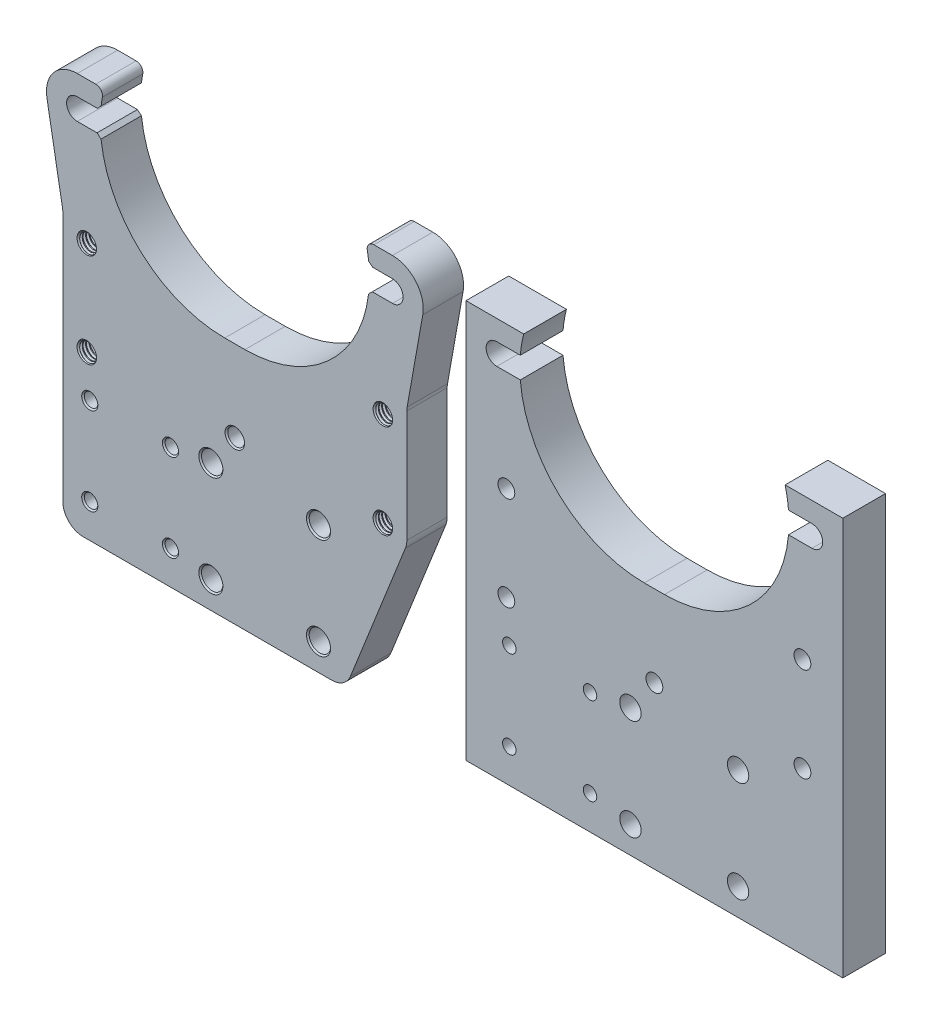
SolidWorks part; units mm, degrees
ref_plane "Front Plane" through (0, 0, 0) normal (0, 0, 1) x (1, 0, 0)
ref_plane "Top Plane" through (0, 0, 0) normal (0, 1, 0) x (1, 0, 0)
ref_plane "Right Plane" through (0, 0, 0) normal (1, 0, 0) x (0, 0, -1)
sketch "Sketch1" plane through (0, 0, 0) normal (0, 0, 1) x (1, 0, 0)
  line L0 (-8, 7.5) -> (8, 7.5) construction
  line L5 (-26, 6.5) -> (-14, 6.5) construction
  line L7 (-8, -7.5) -> (8, -7.5) construction
  line L8 (-8, -7.5) -> (-8, 7.5) construction
  line L9 (-8, 7.5) -> (8, 7.5) construction
  line L10 (8, -7.5) -> (8, 7.5) construction
  line L11 (-8, -7.5) -> (8, 7.5) construction
  line L12 (-8, 7.5) -> (8, -7.5) construction
  line L13 (-8, 7.5) -> (-8, -7.5) construction
  line L14 (-26, -6.5) -> (-14, -6.5) construction
  line L15 (-26, -6.5) -> (-26, 6.5) construction
  line L16 (-26, 6.5) -> (-14, 6.5) construction
  line L17 (-14, -6.5) -> (-14, 6.5) construction
  line L18 (-26, -6.5) -> (-14, 6.5) construction
  line L19 (-26, 6.5) -> (-14, -6.5) construction
  line L20 (0, 0) -> (-20, 0) construction
  line L21 (-6.4375, 59.6343) -> (-6.4375, -58.2445) construction
  line L22 (-30, -11.5) -> (12, -11.5)
  line L23 (-30, -11.5) -> (-30, 11.5)
  line L24 (-30, 11.5) -> (12, 11.5)
  line L25 (12, -11.5) -> (12, 11.5)
  line L26 (-30, -11.5) -> (12, 11.5) construction
  line L27 (-30, 11.5) -> (12, -11.5) construction
  line L28 (-11.5, -15) -> (-28.5, -15) construction
  line L29 (-11.5, -15) -> (-11.5, 15) construction
  line L30 (-11.5, 15) -> (-28.5, 15) construction
  line L31 (-28.5, -15) -> (-28.5, 15) construction
  line L32 (-11.5, -15) -> (-28.5, 15) construction
  line L33 (-11.5, 15) -> (-28.5, -15) construction
  line L34 (-59, 15) -> (41, 15) construction
  line L35 (-59, 15) -> (-59, 24) construction
  line L36 (-59, 24) -> (41, 24) construction
  line L37 (41, 15) -> (41, 24) construction
  line L38 (-59, -10) -> (41, -10) construction
  line L39 (-59, -10) -> (-59, 10) construction
  line L40 (-59, 10) -> (41, 10) construction
  line L41 (41, -10) -> (41, 10) construction
  line L42 (-59, -10) -> (41, 10) construction
  line L43 (-59, 10) -> (41, -10) construction
  line L44 (-30, -11.5) -> (12, -11.5)
  line L45 (-30, -11.5) -> (-30, 29)
  line L46 (-30, 29) -> (12, 29)
  line L47 (12, -11.5) -> (12, 29)
  line L48 (-4.4375, 43.1) -> (17.4825, 43.1) construction
  line L49 (-4.4375, 43.1) -> (-26.3575, 43.1) construction
  line L50 (-24.8575, 43.1) -> (-27.8575, 43.1) construction
  line L51 (-24.8575, 41.5125) -> (-27.8575, 41.5125)
  line L52 (-24.8575, 44.6875) -> (-27.8575, 44.6875)
  line L53 (15.9825, 43.1) -> (18.9825, 43.1) construction
  line L54 (15.9825, 44.6875) -> (18.9825, 44.6875)
  line L55 (15.9825, 41.5125) -> (18.9825, 41.5125)
  line L56 (-24.8575, 44.6875) -> (-22.8693, 44.6875)
  line L57 (-24.8575, 41.5125) -> (-22.8693, 41.5125)
  line L58 (15.9825, 41.5125) -> (13.9943, 41.5125)
  line L59 (15.9825, 44.6875) -> (13.9943, 44.6875)
  line L60 (-4.4375, 43.1) -> (-4.4375, 61.6) construction
  line L61 (12, -11.5) -> (21.125, 11.5)
  line L62 (21.125, 11.5) -> (21.125, 29)
  line L63 (21.125, 29) -> (12, 29)
  line L64 (18.9825, 47.68) -> (14.874, 47.68)
  line L65 (21.125, 29) -> (23.4916, 42.2975)
  line L66 (-30, 29) -> (-32.3666, 42.2975)
  line L67 (-5.9375, 43.1) -> (-2.9375, 43.1) construction
  line L68 (-5.9375, 61.6) -> (-2.9375, 61.6)
  line L69 (-5.9375, 24.6) -> (-2.9375, 24.6)
  line L70 (23.5625, -11.5) -> (13.5725, -7.5366) construction
  line L71 (-32.4375, 47.68) -> (23.5625, 47.68)
  line L72 (-6.4375, 19.5) -> (6.6756, 19.5) construction
  line L73 (-27.8575, 47.68) -> (-23.8616, 47.68)
  line L74 (-32.4375, 47.68) -> (-32.4375, -11.5)
  line L75 (-32.4375, -11.5) -> (23.5625, -11.5)
  line L76 (23.5625, 47.68) -> (23.5625, -11.5)
  circle A0 centre (-8, 7.5) radius 1.5875
  circle A2 centre (8, 7.5) radius 1.5875
  circle A3 centre (8, -7.5) radius 1.5875
  circle A4 centre (-8, -7.5) radius 1.5875
  circle A5 centre (-26, 6.5) radius 1
  circle A6 centre (-14, 6.5) radius 1
  circle A7 centre (-14, -6.5) radius 1
  circle A8 centre (-26, -6.5) radius 1
  circle A9 centre (-8, 7.5) radius 2.9 construction
  circle A10 centre (-14, 6.5) radius 2
  circle A11 centre (-26, 6.5) radius 2
  circle A12 centre (-26, -6.5) radius 2
  circle A13 centre (-14, -6.5) radius 2
  circle A14 centre (-4.4375, 43.1) radius 2 construction
  circle A15 centre (-4.4375, 43.1) radius 8 construction
  circle A16 centre (-4.4375, 43.1) radius 18.5
  circle A17 centre (17.4825, 43.1) radius 1.5875 construction
  circle A18 centre (-26.3575, 43.1) radius 1.5875 construction
  arc A19 (-24.8575, 41.5125) -> (-24.8575, 44.6875) centre (-24.8575, 43.1) ccw
  arc A20 (-27.8575, 44.6875) -> (-27.8575, 41.5125) centre (-27.8575, 43.1) ccw
  arc A21 (15.9825, 44.6875) -> (15.9825, 41.5125) centre (15.9825, 43.1) ccw
  arc A22 (18.9825, 41.5125) -> (18.9825, 44.6875) centre (18.9825, 43.1) ccw
  arc A23 (-5.9375, 61.6) -> (-5.9375, 24.6) centre (-5.9375, 43.1) ccw
  arc A24 (-2.9375, 24.6) -> (-2.9375, 61.6) centre (-2.9375, 43.1) ccw
  circle A25 centre (-26.4375, 26.5) radius 1.25
  circle A26 centre (-26.4375, 12.5) radius 1.25
  circle A29 centre (17.5625, 12.5) radius 1.25
  circle A30 centre (17.5625, 26.5) radius 1.25
  circle A31 centre (-27.8575, 43.1) radius 4.58
  circle A32 centre (18.9825, 43.1) radius 4.58
  circle A33 centre (17.5625, 26.5) radius 2.9 construction
  circle A34 centre (17.5625, 12.5) radius 2.9 construction
  circle A35 centre (-4.4375, 12.5) radius 1.25
  point P0 (0, 0)
  point P1 (-20, 0)
  point P4 (-9, 0)
  point P6 (0, 0)
  point P46 (-9, 15)
  point P47 (-9, 0)
  point P70 (-26.3575, 43.1)
  point P77 (17.4825, 43.1)
  point P97 (-4.4375, 43.1)
  dimension "D5" = 3.175
  dimension "D6" = 2
  dimension "D18" = 5.8
  dimension "D27" = 4
  dimension "D29" = 4
  dimension "D30" = 16
  dimension "D31" = 37
  dimension "D33" = 3.175
  dimension "D35" = 1.5875
  dimension "D40" = 18.5
  dimension "D43" = 2.5
  dimension "D39" = 9.16
  dimension "D48" = 9.16
  dimension "D38" = 5.8
  dimension "D42" = 2.5
  dimension "D1" = 15
  dimension "D2" = 16
  dimension "D3" = 13
  dimension "D4" = 12
  dimension "D9" = 16
  dimension "D10" = 15
  dimension "D13" = 12
  dimension "D14" = 20
  dimension "D15" = 23
  dimension "D16" = 4
  dimension "D17" = 4
  dimension "D19" = 17
  dimension "D20" = 30
  dimension "D21" = 9
  dimension "D22" = 100
  dimension "D23" = 20
  dimension "D24" = 100
  dimension "D25" = 15
  dimension "D26" = 40.5
  dimension "D28" = 13.5625
  dimension "D32" = 21.92
  dimension "D34" = 19.1
  dimension "D36" = 3
  dimension "D37" = 9.125
  dimension "D41" = 3
  dimension "D44" = 20
  dimension "D45" = 4.5
  dimension "D46" = 7
  dimension "D47" = 7
  dimension "D49" = 22
  dimension "D7" = 2
  dimension "D8" = 2
  dimension "D11" = 2
  dimension "D12" = 2
extrude "Boss-Extrude1" add sketch "Sketch1" along normal blind 6 contours A20 L52 L56 A16 L46 L57 L51 | A22 L55 L58 A16 L46 L63 L59 L54 | L62 L63 L47 L25 L61 | A16 L46 L45 L24 L47 | L22 L25 L24 L23 A13 A12 A11 A10 A4 A3 A2 A0 | A10 A6 | A11 A5 | A12 A8 | A13 A7 | A31 L46 A23 | A32 A24 L46 L63 | A31 A23 L73 | A32 L64 A24 region at (-8.6931, -0.0066, 0) region at (15.8976, 13.518, 0) region at (-9.3836, 19.3871, 0) region at (-26.1981, 33.733, 0) region at (-31.0091, 46.2516, 0) region at (17.3231, 33.733, 0) region at (23.4222, 42.708, 0) region at (-24.9644, 47.1601, 0) region at (16.0894, 47.1601, 0) region at (-15.9434, 6.5, 0) region at (-27.9434, 6.5, 0) region at (-27.9434, -6.5, 0) region at (-15.9434, -6.5, 0)
extrude "Cut-Extrude1" cut sketch "Sketch1<3>" along normal blind 2.2 contours A10 A6 | A11 A5 | A12 A8 | A13 A7 | A13 region at (-15.9434, 6.5, 0) region at (-27.9434, 6.5, 0) region at (-27.9434, -6.5, 0) region at (-15.9434, -6.5, 0)
sketch "Sketch1<3>" plane through (0, 0, 0) normal (0, 0, 1) x (1, 0, 0) same geometry as "Sketch1"
chamfer "Chamfer1" distance 0.2 angle 45 26 edges at (-24, 6.5, 0) (-24, -6.5, 0) (-12, -6.5, 0) (-12, 6.5, 0) (-6.4125, -7.5, 0) (9.5875, -7.5, 0) (9.5875, 7.5, 0) (-6.4125, 7.5, 0) (-25, -6.5, 6) (-25, 6.5, 6) (-13, 6.5, 6) (-13, -6.5, 6) (-6.4125, -7.5, 6) (9.5875, -7.5, 6) (9.5875, 7.5, 6) (-6.4125, 7.5, 6) (18.8125, 26.5, 0) (18.8125, 26.5, 6) (18.8125, 12.5, 0) (18.8125, 12.5, 6) (-25.1875, 12.5, 0) (-25.1875, 12.5, 6) (-25.1875, 26.5, 0) (-25.1875, 26.5, 6) (-3.1875, 12.5, 0) (-3.1875, 12.5, 6)
fillet "Fillet1" radius 3 5 edges at (-30, -11.5, 3) (12, -11.5, 3) (21.125, 11.5, 3) (21.125, 29, 3) (-30, 29, 3)
chamfer "Chamfer2" distance 0.5 angle 45 4 edges at (-24.3693, 41.5125, 3) (-24.3693, 44.6875, 3) (15.4943, 44.6875, 3) (15.4943, 41.5125, 3) first distance on face at (-16.7993, 31.2625, 3) first distance on face at (-26.1134, 44.6875, 3) first distance on face at (15.2712, 46.189, 3) first distance on face at (17.2384, 41.5125, 3)
fillet "Fillet4" radius 1 2 edges at (-23.8616, 47.68, 3) (14.9866, 47.68, 3)
thread "Thread1" pitch 0.5 method cut profile "Thread Profile1" start angle 0, offset 1, length 10, pitch 0.5, diameter 2.5
ref_plane "Plane1" through (-27.6875, 26.5, 6.8) normal (0, -1, 0) x (-1, 0, 0)
sketch "Thread Profile1" plane through (-27.6875, 26.5, 6.8) normal (0, -1, 0) x (-1, 0, 0)
  line L0 (0, 0) -> (0, 0.5) construction
  line L1 (0, 0) -> (0.2706, 0.1562)
  line L2 (0.2706, 0.1562) -> (0.2706, 0.2187)
  line L3 (0.2706, 0.2187) -> (0, 0.375)
  line L4 (0.2706, 0.1875) -> (0, 0.1875) construction
  line L11 (0, 0) -> (0, 0.375)
  point P2 (0, 0)
  dimension "Pitch" = 0.5
  dimension "Profile_Angle" = 60
  dimension "Profile_Land" = 0.0625
  dimension "Profile_Height" = 0.2706
pattern_linear "LPattern1" count 2 spacing 44 along (1, 0, 0) count 2 spacing 14 along (0, -1, 0) of "Thread1"
extrude "Boss-Extrude3" add sketch "Sketch1<5>" along normal blind 6.35 separate body contours L23 L45 | A23 L46 L57 L51 A20 L52 L56 | A26 L24 L47 L46 A24 L69 A23 L45 A25 | A26 L24 L23 L22 L25 A13 A12 A11 A10 A4 A3 A2 A0 | L62 L63 L47 L25 L61 A29 A30 | L62 L61 | A24 L59 L54 A22 L55 L58 L46 L63 | A10 A6 | A11 A5 | A12 A8 | A13 A7 | A31 L66 L46 A23 | A32 A24 L46 L63 L65 | A31 L71 L74 | A31 A23 L71 | A32 L76 L71 | A32 L64 A24 region at (-8.6931, -0.0066, 0) region at (-31.2776, 12.3402, 0) region at (15.8976, 13.518, 0) region at (20.3456, 4.638, 0) region at (-9.3836, 19.3871, 0) region at (-26.1981, 33.733, 0) region at (-31.4145, 46.657, 0) region at (-31.0091, 46.2516, 0) region at (17.3231, 33.733, 0) region at (22.5395, 46.657, 0) region at (23.4222, 42.708, 0) region at (-24.9644, 47.1601, 0) region at (16.0894, 47.1601, 0) region at (-15.9434, 6.5, 0) region at (-27.9434, 6.5, 0) region at (-27.9434, -6.5, 0) region at (-15.9434, -6.5, 0)
sketch "Sketch1<5>" plane through (0, 0, 0) normal (0, 0, 1) x (1, 0, 0) same geometry as "Sketch1"
extrude "Cut-Extrude2" cut sketch "Sketch1<7>" along normal blind 2.2 contours A10 A6 | A11 A5 | A12 A8 | A13 A7 region at (-15.9434, 6.5, 0) region at (-27.9434, 6.5, 0) region at (-27.9434, -6.5, 0) region at (-15.9434, -6.5, 0)
sketch "Sketch1<7>" plane through (0, 0, 0) normal (0, 0, 1) x (1, 0, 0) same geometry as "Sketch1"
move or copy body "Body-Move/Copy1" bodies to move or copy 109 copy no translate (62.7049, 0, 0)
